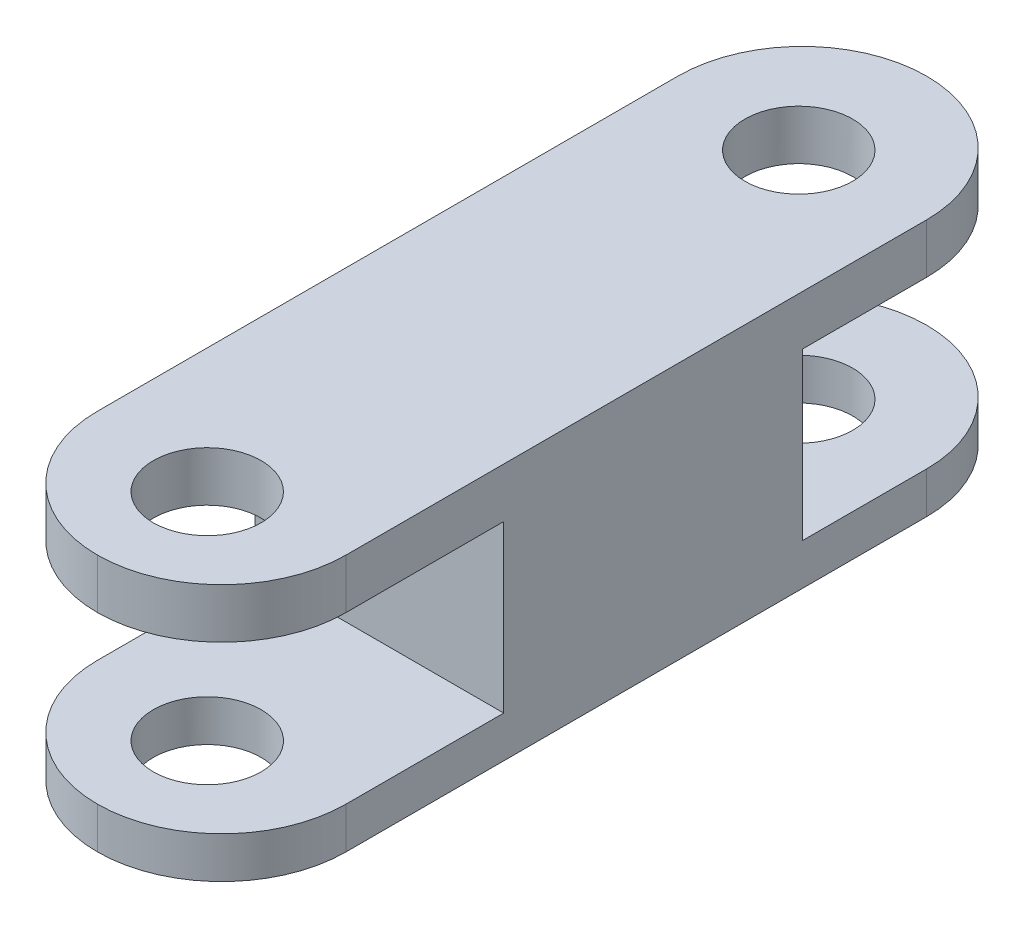
SolidWorks part; units mm, degrees
ref_plane "Front Plane" through (0, 0, 0) normal (0, 0, 1) x (1, 0, 0)
ref_plane "Top Plane" through (0, 0, 0) normal (0, 1, 0) x (1, 0, 0)
ref_plane "Right Plane" through (0, 0, 0) normal (1, 0, 0) x (0, 0, -1)
sketch "Sketch1" plane through (0, 0, 0) normal (0, 1, 0) x (1, 0, 0)
  line L0 (0, -32.8041) -> (0, -58.2041)
extrude "Extrude-Thin1" add sketch "Sketch1" along normal blind 7.874 thin contours L0 thin type one direction wall 7.62
fillet "Fillet1" radius 3.81 4 edges at (-7.62, 3.937, 32.8041) (0, 3.937, 32.8041) (0, 3.937, 58.2041) (-7.62, 3.937, 58.2041)
sketch "Sketch3" plane through (0, 7.874, 0) normal (0, 1, 0) x (1, 0, 0)
  circle A0 centre (-3.8056, -54.8416) radius 1.651
extrude "Cut-Extrude1" cut sketch "Sketch3" against normal blind 7.874
pattern_linear "LPattern1" count 2 spacing 18.1153 along (0, 0, -1) of "Cut-Extrude1"
sketch "Sketch5" plane through (0, 0, 0) normal (1, 0, 0) x (0, 0, -1)
  line L0 (-36.6141, 6.3483) -> (-36.6141, 1.2683)
  line L1 (-36.6141, 0) -> (-36.6141, 7.874) construction
  point P5 (-36.6141, 3.8083)
extrude "Cut-Extrude-Thin1" cut sketch "Sketch5" against normal through all both and the other way through all flip side to cut thin thin type one direction wall 3.81
extrude "Cut-Extrude-Thin2" cut sketch "Sketch5<3>" against normal blind 7.874 and the other way through all thin thin type one direction reverse wall 5.08
sketch "Sketch5<3>" plane through (0, 0, 0) normal (1, 0, 0) x (0, 0, -1) same geometry as "Sketch5"
pattern_linear "LPattern2" count 2 spacing 18.034 along (0, 0, 1) of "Cut-Extrude-Thin2"
pattern_linear "LPattern4" count 2 spacing 18.034 along (0, 0, 1) of "Cut-Extrude-Thin1"
